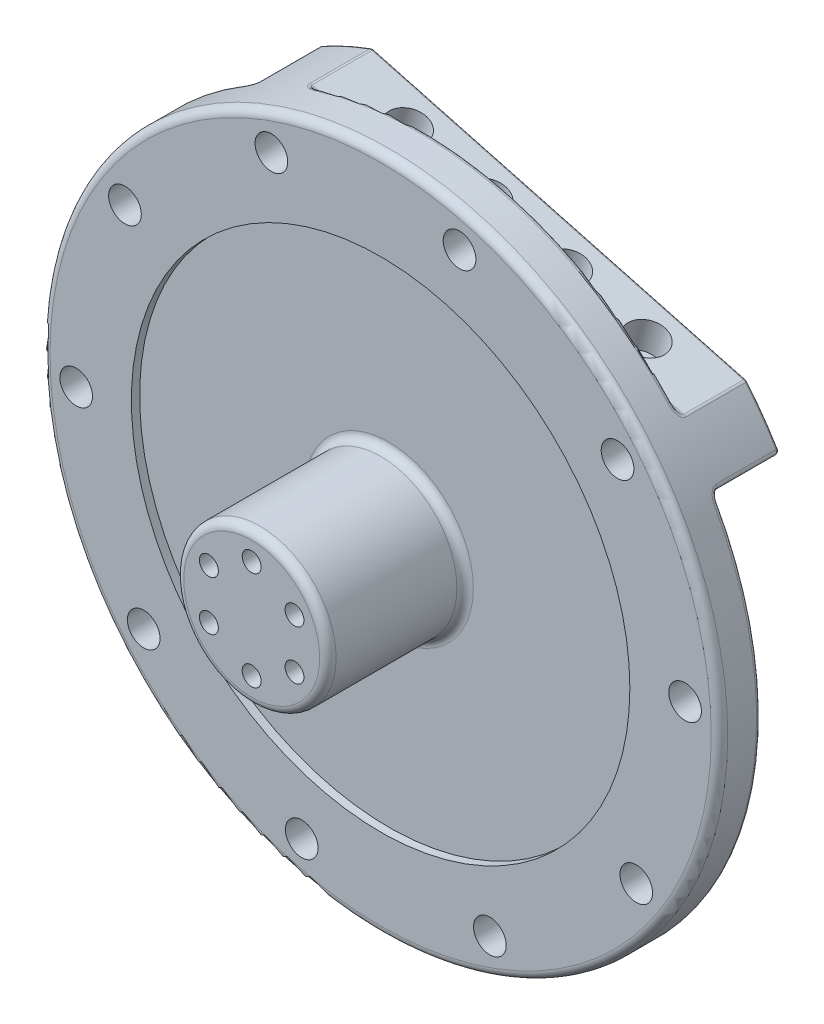
SolidWorks part; units mm, degrees
material "Custom PLA"
ref_plane "Front Plane" through (0, 0, 0) normal (0, 0, 1) x (1, 0, 0)
ref_plane "Top Plane" through (0, 0, 0) normal (0, 1, 0) x (1, 0, 0)
ref_plane "Right Plane" through (0, 0, 0) normal (1, 0, 0) x (0, 0, -1)
sketch "Sketch1" plane through (0, 0, 0) normal (0, 0, 1) x (1, 0, 0)
  circle A0 centre (0, 0) radius 82.25
  circle A1 centre (0, 0) radius 74 construction
  circle A2 centre (0, 74) radius 2.75
  dimension "D1" = 164.5
  dimension "D2" = 148
  dimension "D3" = 5.5
extrude "Boss-Extrude1" add sketch "Sketch1" along normal blind 10 contours A0
sketch "Sketch3" plane through (0, 0, 10) normal (0, 0, 1) x (1, 0, 0)
  circle A0 centre (0, 74) radius 4.065
  circle A1 centre (0, 0) radius 74 construction
  dimension "D1" = 8.13
  dimension "D2" = 148
extrude "Cut-Extrude6" [suppressed] cut sketch "Sketch3" against normal blind 6.7 contours A0
pattern_circular "CirPattern1" [suppressed] count 10 over 360 of bodies 102
sketch "Sketch13" plane through (0, 0, 10) normal (0, 0, 1) x (1, 0, 0)
  circle A0 centre (0, 0) radius 60.5
  dimension "D1" = 121
extrude "Cut-Extrude12" cut sketch "Sketch13" against normal blind 2 contours A0
sketch "Sketch4" plane through (0, 0, 8) normal (0, 0, 1) x (1, 0, 0)
  circle A0 centre (0, 0) radius 18.5
  dimension "D1" = 37
extrude "Boss-Extrude2" add sketch "Sketch4" along normal blind 33.3 contours A0
sketch "Sketch5" plane through (0, 0, 0) normal (0, 0, -1) x (-1, 0, 0)
  circle A0 centre (0, 0) radius 17
  dimension "D1" = 34
extrude "Cut-Extrude7" cut sketch "Sketch5" against normal blind 36.3
sketch "Sketch6" plane through (0, 0, 36.3) normal (0, 0, -1) x (-1, 0, 0)
  line L0 (0, 17) -> (0, -17) construction
  circle A0 centre (0, 0) radius 12 construction
  circle A1 centre (0, 0) radius 17 construction
  circle A2 centre (0, 0) radius 17 construction
  circle A3 centre (0, 12) radius 2.3
  dimension "D1" = 24
  dimension "D2" = 4.6
extrude "Cut-Extrude8" cut sketch "Sketch6" against normal through all
pattern_circular "CirPattern2" count 6 over 360 about axis through (0, 0, 36.3) along (0, 0, -1) of "Cut-Extrude8"
sketch "Sketch7" plane through (0, 0, 0) normal (0, 0, -1) x (-1, 0, 0)
  line L0 (0, 82.25) -> (0, -82.25) construction
  line L1 (41.9236, 70.7635) -> (-71.6886, 40.3212)
  line L6 (27.9235, 77.365) -> (-62.8649, 53.0383)
  line L7 (-82.25, 0) -> (82.25, 0) construction
  line L8 (0, 0) -> (-21.2879, 79.4474) construction
  line L9 (0, 0) -> (79.4474, 21.2879) construction
  line L10 (79.4474, 21.2879) -> (-79.4474, -21.2879) construction
  line L11 (62.8649, -53.0383) -> (-27.9235, -77.365)
  line L12 (71.6886, -40.3212) -> (-41.9236, -70.7635)
  circle A0 centre (0, 0) radius 82.25 construction
  arc A1 (41.9236, 70.7635) -> (27.9235, 77.365) centre (0, 0) ccw
  arc A2 (-71.6886, 40.3212) -> (-62.8649, 53.0383) centre (0, 0) cw
  arc A3 (71.6886, -40.3212) -> (62.8649, -53.0383) centre (0, 0) cw
  arc A4 (-41.9236, -70.7635) -> (-27.9235, -77.365) centre (0, 0) ccw
  point P9 (-14.8825, 55.5424)
  dimension "D2" = 117.62
  dimension "D1" = 10
  dimension "D3" = 90
  dimension "D4" = 15
extrude "Boss-Extrude3" add sketch "Sketch7" along normal blind 16
mirror "Mirror1" [suppressed] about plane through (0, 0, 0) normal (1, 0, 0)
sketch "Sketch8" plane through (17.4707, 65.2016, 0) normal (0.2588, 0.9659, 0) x (-0.9659, 0.2588, 0)
  line L0 (0, 0) -> (0, -16) construction
  line L1 (46.9956, -16) -> (-46.9956, -16) construction
  line L2 (-46.9956, -8) -> (46.9956, -8) construction
  line L3 (-46.9956, -16) -> (-46.9956, 0) construction
  line L4 (46.9956, -16) -> (46.9956, 0) construction
  line L5 (-20, 0) -> (-20, -16) construction
  line L6 (46.9956, 0) -> (-46.9956, 0) construction
  line L7 (-30, 0) -> (-30, -16) construction
  circle A0 centre (-30, -8) radius 4.56
  dimension "D3" = 9.12
  dimension "D1" = 20
  dimension "D2" = 10
extrude "Cut-Extrude9" cut sketch "Sketch8" against normal blind 7.62 contours A0
pattern_linear "LPattern1" count 4 spacing 20 along (-0.9659, 0.2588, 0) of "Cut-Extrude9"
mirror "Mirror2" [suppressed] about plane through (0, 0, 0) normal (1, 0, 0)
sketch "Sketch9" plane through (0, 0, 10) normal (0, 0, 1) x (1, 0, 0)
  line L0 (0, 82.25) -> (0, -82.25) construction
  line L1 (0, 0) -> (19.1526, 71.4785) construction
  circle A0 centre (0, 0) radius 74 construction
  circle A1 centre (19.1526, 71.4785) radius 3.965
  circle A2 centre (0, 0) radius 82.25 construction
  dimension "D1" = 148
  dimension "D2" = 7.93
  dimension "D3" = 15
extrude "Cut-Extrude10" cut sketch "Sketch9" against normal blind 6.73
pattern_circular "CirPattern3" count 10 over 360 about axis through (0, 0, 10) along (0, 0, 1) of "Cut-Extrude10"
sketch "Sketch12" plane through (-17.4707, -65.2016, 0) normal (-0.2588, -0.9659, 0) x (0.9659, -0.2588, 0)
  line L0 (0, -16) -> (0, 0) construction
  line L1 (46.9956, -16) -> (-46.9956, -16) construction
  line L2 (46.9956, -8) -> (-46.9956, -8) construction
  line L3 (46.9956, -16) -> (46.9956, 0) construction
  line L4 (-46.9956, -16) -> (-46.9956, 0) construction
  line L5 (30, -16) -> (30, 0) construction
  line L6 (-46.9956, 0) -> (46.9956, 0) construction
  circle A0 centre (30, -8) radius 4.56
  dimension "D2" = 9.12
  dimension "D1" = 30
extrude "Cut-Extrude11" cut sketch "Sketch12" against normal blind 7.62
pattern_linear "LPattern2" count 4 spacing 20 along (-0.9659, 0.2588, 0) of "Cut-Extrude11"
fillet "Fillet1" radius 2 3 edges at (18.5, 0, 41.3) (82.25, 0, 10) (18.5, 0, 8)
fillet "Fillet2" radius 1 9 edges at (41.9236, -70.7635, -8) (71.6886, 40.3212, -8) (-41.9236, 70.7635, -8) (-71.6886, -40.3212, -8) (79.4474, -21.2879, 0) (14.8825, 55.5424, 0) (-79.4474, 21.2879, 0) (-14.8825, -55.5424, 0) (-17, 0, 0)
fillet "Fillet3" radius 1 8 edges at (62.8649, 53.0383, -8) (-27.9235, 77.365, -8) (-62.8649, -53.0383, -8) (27.9235, -77.365, -8) (21.2879, 79.4474, 0) (17.4707, 65.2016, 0) (-21.2879, -79.4474, 0) (-17.4707, -65.2016, 0)
fillet "Fillet4" radius 0.5 16 edges at (-70.4027, -41.3137, -16) (-66.9654, -47.7566, -16) (-62.8398, -52.9969, -16) (-17.4707, -65.2016, -16) (27.9224, -77.3166, -16) (34.1154, -74.8412, -16) (40.3136, -70.9801, -16) (70.4027, 41.3137, -16) (66.9654, 47.7566, -16) (62.8398, 52.9969, -16) (17.4707, 65.2016, -16) (-27.9224, 77.3166, -16) (-34.1154, 74.8412, -16) (-40.3136, 70.9801, -16) (-14.8825, -55.5424, -16) (14.8825, 55.5424, -16)
ref_plane "Plane1" [suppressed] through (0, 0, 8) normal (0, 0, 1) x (1, 0, 0)
